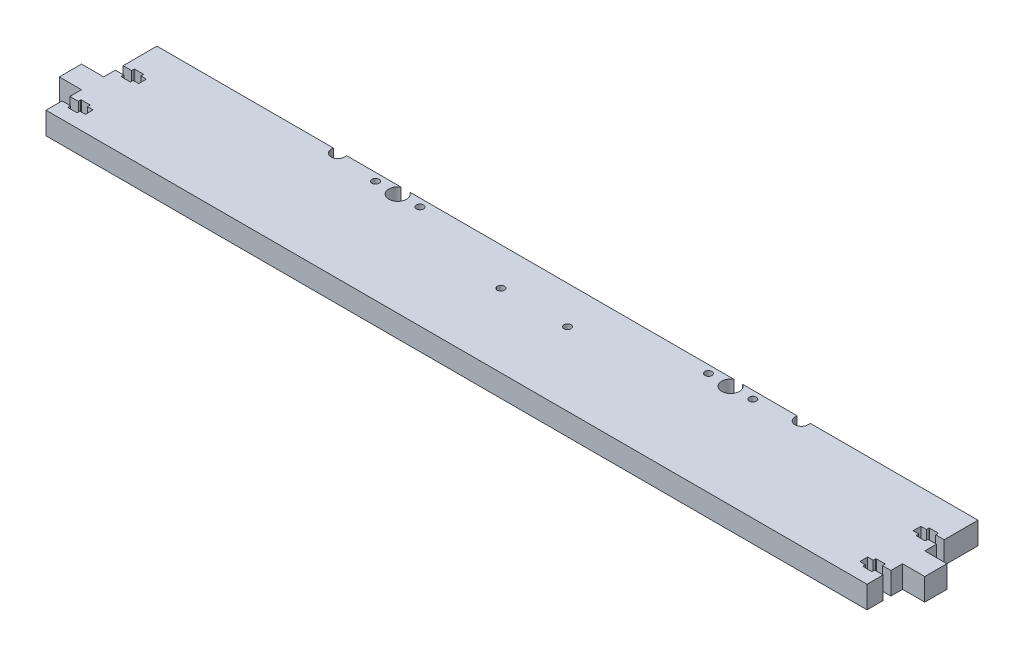
SolidWorks part; units mm, degrees
ref_plane "Front Plane" through (0, 0, 0) normal (0, 0, 1) x (1, 0, 0)
ref_plane "Top Plane" through (0, 0, 0) normal (0, 1, 0) x (1, 0, 0)
ref_plane "Right Plane" through (0, 0, 0) normal (1, 0, 0) x (0, 0, -1)
sketch "Sketch1" plane through (0, 0, 0) normal (0, 1, 0) x (1, 0, 0)
  line L0 (0, 25) -> (0, -25)
  line L1 (-185, 25) -> (0, 25)
  line L2 (-185, 25) -> (-185, -25) construction
  line L3 (-185, -25) -> (0, -25)
  line L4 (-185, -4) -> (-195, -4) construction
  line L5 (-185, 25) -> (0, 0) construction
  line L6 (-185, -25) -> (0, 0) construction
  line L7 (-185, -9) -> (-195, -9)
  line L8 (-195, -9) -> (-195, 1)
  line L9 (-195, 1) -> (-185, 1)
  line L10 (-185, 1) -> (-185, 25)
  line L11 (-185, -9) -> (-185, -25)
  line L47 (0, -25) -> (0, 25) construction
  line L89 (0, -25) -> (0, 25) construction
  point P0 (0, 0)
  dimension "D1" = 185
  dimension "D25" = 25
  dimension "D4" = 50
  dimension "D3" = 21
  dimension "D5" = 10
  dimension "D6" = 10
  dimension "D7" = 5
extrude "MainBody" add sketch "Sketch1" along normal blind 10 contours L3 region at (-93.5428, 0, 0.0428)
sketch "Sketch5" plane through (0, 10, 0) normal (0, 1, 0) x (1, 0, 0)
  line L0 (-185, 8) -> (-174.5, 8) construction
  line L1 (-185, 1) -> (-185, 25) construction
  line L2 (-185, 9.75) -> (-174.5, 9.75) construction
  line L3 (-174.5, 9.75) -> (-174.5, 6.25) construction
  line L4 (-174.5, 6.25) -> (-185, 6.25) construction
  line L5 (-185, 9.75) -> (-181.2, 9.75)
  line L6 (-181.2, 9.75) -> (-181.2, 10.75)
  line L7 (-180.95, 11) -> (-177.25, 11)
  line L8 (-177, 10.75) -> (-177, 9.75)
  line L9 (-177, 9.75) -> (-174.5, 9.75)
  line L10 (-174.5, 9.75) -> (-174.5, 6.25)
  line L11 (-185, 6.25) -> (-185, 9.75)
  line L12 (-195, -9) -> (-195, 1) construction
  line L13 (-185, 6.25) -> (-174.5, 6.25) construction
  line L14 (-177, 6.25) -> (-174.5, 6.25)
  line L15 (-177, 5.25) -> (-177, 6.25)
  line L16 (-180.95, 5) -> (-177.25, 5)
  line L17 (-181.2, 6.25) -> (-181.2, 5.25)
  line L18 (-185, 6.25) -> (-181.2, 6.25)
  line L19 (-185, 1) -> (-185, -9) construction
  line L20 (-195, -4) -> (-185, -4) construction
  line L21 (-195, -9) -> (-195, 1) construction
  line L22 (-185, -14.25) -> (-174.5, -14.25) construction
  line L23 (-174.5, -14.25) -> (-185, -14.25) construction
  line L24 (-174.5, -17.75) -> (-174.5, -14.25) construction
  line L25 (-185, -17.75) -> (-174.5, -17.75) construction
  line L26 (-185, -16) -> (-174.5, -16) construction
  line L27 (-185, -14.25) -> (-181.2, -14.25)
  line L28 (-181.2, -14.25) -> (-181.2, -13.25)
  line L29 (-180.95, -13) -> (-177.25, -13)
  line L30 (-177, -13.25) -> (-177, -14.25)
  line L31 (-177, -14.25) -> (-174.5, -14.25)
  line L32 (-185, -14.25) -> (-185, -17.75)
  line L33 (-174.5, -17.75) -> (-174.5, -14.25)
  line L34 (-177, -17.75) -> (-174.5, -17.75)
  line L35 (-177, -18.75) -> (-177, -17.75)
  line L36 (-180.95, -19) -> (-177.25, -19)
  line L37 (-181.2, -17.75) -> (-181.2, -18.75)
  line L38 (-185, -17.75) -> (-181.2, -17.75)
  line L39 (-185, 6.25) -> (-174.5, 6.25) construction
  arc A0 (-177.25, 11) -> (-177, 10.75) centre (-177.25, 10.75) cw
  arc A1 (-181.2, 10.75) -> (-180.95, 11) centre (-180.95, 10.75) cw
  arc A2 (-181.2, 5.25) -> (-180.95, 5) centre (-180.95, 5.25) ccw
  arc A3 (-177.25, 5) -> (-177, 5.25) centre (-177.25, 5.25) ccw
  arc A4 (-177.25, -13) -> (-177, -13.25) centre (-177.25, -13.25) cw
  arc A5 (-181.2, -13.25) -> (-180.95, -13) centre (-180.95, -13.25) cw
  arc A6 (-181.2, -18.75) -> (-180.95, -19) centre (-180.95, -18.75) ccw
  arc A7 (-177.25, -19) -> (-177, -18.75) centre (-177.25, -18.75) ccw
  point P6 (-195, -4)
  point P17 (-177, 11)
  point P20 (-181.2, 11)
  point P29 (-181.2, 5)
  point P30 (-177, 5)
  point P61 (-177, -13)
  point P62 (-181.2, -13)
  point P63 (-181.2, -19)
  point P64 (-177, -19)
  dimension "D8" = 0.25
  dimension "D1" = 10.5
  dimension "D2" = 1.75
  dimension "D4" = 4.2
  dimension "D5" = 8
  dimension "D6" = 3
  dimension "D7" = 12
extrude "ScrewCutouts" cut sketch "Sketch5" against normal through all
mirror "Mirror1" about plane through (0, 0, 0) normal (1, 0, 0) of "ScrewCutouts", "MainBody"
sketch "Sketch3" plane through (0, 10, 0) normal (0, 1, 0) x (1, 0, 0)
  line L0 (2, 25) -> (2, -25) construction
  line L1 (-185, 25) -> (185, 25) construction
  line L2 (-185, -25) -> (185, -25) construction
  line L3 (-63, 21.5) -> (-83, 21.5) construction
  line L4 (-73, 17.5) -> (-73, 25.5) construction
  line L5 (77, 17.5) -> (77, 25.5) construction
  line L6 (67, 21.5) -> (87, 21.5) construction
  circle A0 centre (-73, 21.5) radius 4
  circle A1 centre (-83, 21.5) radius 1.6
  circle A2 centre (-63, 21.5) radius 1.6
  circle A3 centre (67, 21.5) radius 1.6
  circle A4 centre (87, 21.5) radius 1.6
  circle A5 centre (77, 21.5) radius 4
  dimension "D2" = 8
  dimension "D4" = 3.2
  dimension "D1" = 3.5
  dimension "D3" = 10
  dimension "D5" = 75
  dimension "D6" = 2
extrude "RodCutouts" cut sketch "Sketch3" against normal through all
sketch "Sketch6" plane through (0, 10, 0) normal (0, 1, 0) x (1, 0, 0)
  line L0 (-73, 21.5) -> (77, 21.5) construction
  line L1 (2, 21.5) -> (2, -25) construction
  line L2 (-185, -25) -> (185, -25) construction
  line L3 (17, 8) -> (-13, 8) construction
  line L4 (-71.0635, 25) -> (75.0635, 25) construction
  circle A0 centre (-13, 8) radius 1.6
  circle A1 centre (17, 8) radius 1.6
  point P13 (2, 8)
  dimension "D1" = 3.2
  dimension "D2" = 15
  dimension "D3" = 17
extrude "Cut-Extrude1" cut sketch "Sketch6" against normal through all
sketch "Sketch7" plane through (0, 10, 0) normal (0, 1, 0) x (1, 0, 0)
  line L0 (-73, 21.5) -> (77, 21.5) construction
  line L1 (2, 21.5) -> (2, -25) construction
  line L3 (-102.5, 25) -> (-102.5, 24) construction
  line L4 (-185, 25) -> (-74.9365, 25) construction
  line L5 (-99.5, 25) -> (-99.5, 24)
  line L6 (-105.5, 25) -> (-105.5, 24)
  line L7 (106.5, 25) -> (106.5, 24) construction
  line L8 (103.5, 25) -> (103.5, 24)
  line L9 (109.5, 25) -> (109.5, 24)
  line L12 (-185, -25) -> (185, -25) construction
  arc A0 (-99.5, 25) -> (-105.5, 25) centre (-102.5, 25) ccw
  arc A1 (-105.5, 24) -> (-99.5, 24) centre (-102.5, 24) ccw
  arc A2 (103.5, 25) -> (109.5, 25) centre (106.5, 25) cw
  arc A3 (109.5, 24) -> (103.5, 24) centre (106.5, 24) cw
  point P12 (-102.5, 24.5)
  point P19 (106.5, 24.5)
  dimension "D1" = 3
  dimension "D2" = 1
  dimension "D3" = 104.5
extrude "BedAdjustmentScrewCutout" cut sketch "Sketch7" against normal through all
equation "\"Y-ROD-SPACING\"=75"
equation "\"Y-BED-OFFSET\"=2"
equation "\"T-SLOT-NUT-FILLET-RADIUS\"=0.25"
equation "\"T-SLOT-SCREW-SHAFT-RADIUS\"=1.75"
equation "\"T-SLOT-SCREW-SHAFT-CUTOUT-LENGTH\"=10.5"
equation "\"T-SLOT-NUT-DEPTH\"=4.2"
equation "\"T-SLOT-NUT-WIDTH\"=3"
equation "\"T-SLOT-NUT-END-DISTANCE\"=8"
equation "\"ACRYLIC-TAB-CUTOUT-SIZE\"=\"ACRYLIC-THICKNESS\"+\"ACRYLIC-TAB-TOLERANCE\"*2"
equation "\"ACRYLIC-M3-HOLE\"=3.2"
equation "\"D1@Sketch5\"=\"T-SLOT-SCREW-SHAFT-CUTOUT-LENGTH\""
equation "\"D2@Sketch5\"=\"T-SLOT-SCREW-SHAFT-RADIUS\""
equation "\"D4@Sketch5\"=\"T-SLOT-NUT-DEPTH\""
equation "\"D5@Sketch5\"=\"T-SLOT-NUT-END-DISTANCE\""
equation "\"D6@Sketch5\"=\"T-SLOT-NUT-WIDTH\""
equation "\"D8@Sketch5\"=\"T-SLOT-NUT-FILLET-RADIUS\""
equation "\"D4@Sketch3\"=\"ACRYLIC-M3-HOLE\""
equation "\"D5@Sketch3\"=\"Y-ROD-SPACING\""
equation "\"D6@Sketch3\"=\"Y-BED-OFFSET\""
equation "\"Y-BED-ROD-INSET\"=3.5"
equation "\"D1@Sketch3\"=\"Y-BED-ROD-INSET\""
equation "\"SMOOTHROD-CAP-SCREW-DISTANCE\"=20"
equation "\"D3@Sketch3\"=\"SMOOTHROD-CAP-SCREW-DISTANCE\"/2"
equation "\"ACRYLIC-TAB-WIDTH\"=\"ACRYLIC-THICKNESS\""
equation "\"FRAME-WIDTH-INNER\"=370"
equation "\"D6@Sketch1\"=\"ACRYLIC-TAB-WIDTH\""
equation "\"D5@Sketch1\"=\"ACRYLIC-TAB-WIDTH\""
equation "\"D1@Sketch1\"=\"FRAME-WIDTH-INNER\"/2"
equation "\"X-ROD-SPACING\"=45"
equation "\"Z-ROD-SPACING\"=17.5"
equation "\"ACRYLIC-THICKNESS\"=10"
equation "\"ACRYLIC-THICKNESS2\"=4.5"
equation "\"NEMA17-HOLE-SPACING\"=31"
equation "\"NEMA17-CENTRAL-CUTOUT\"=22.5"
equation "\"Z-BRACKET-REACH\"=55"
equation "\"TOP-BRACKET-SPACING\"=40"
equation "\"SMOOTHROD-X-LENGTH\"=350"
equation "\"SMOOTHROD-Y-LENGTH\"=350"
equation "\"SMOOTHROD-Z-LENGTH\"=350"
equation "\"SMOOTHROD-TIGHTENING-HEADROOM\"=1"
equation "\"LEADSCREW-Z-LENGTH\"=300"
equation "\"SCREW-LENGTH-FRAME\"=\"ACRYLIC-THICKNESS\" + 10"
equation "\"SCREW-HEAD-RADIUS\"=6"
equation "\"PRINTED-X-SMOOTHROD-DIAMETER\"=8.2"
equation "\"PRINTED-X-SMOOTHROD-CUTOUT\"=10"
equation "\"PRINTED-X-BASE-HEIGHT\"=10"
equation "\"PRINTED-LM8UU-CUTOUT-SIZE\"=16"
equation "\"PRINTED-LM8UU-CUTOUT-LENGTH\"=24.5"
equation "\"PRINTED-X-IDLER-HEIGHT\"=16"
equation "\"PSU-MOUNTING-WIDTH\"=95"
equation "\"PSU-MOUNTING-HEIGHT\"=177"
equation "\"D1@MainBody\"=\"ACRYLIC-THICKNESS\""
equation "\"D7@Sketch1\"=\"ACRYLIC-TAB-WIDTH\"/2"
equation "\"D1@Sketch6\"=\"ACRYLIC-M3-HOLE\""
equation "\"Y-BELT-TO-ROD-DISTANCE\"=20"
equation "\"Y-BED-SCREW-SPACING\"=209"
equation "\"Z-ROD-INSET\"=16"
equation "\"SPOOL-HOLDER-ROD-SPACING\"=150"
equation "\"D3@Sketch7\"=\"Y-BED-SCREW-SPACING\"/2"
equation "\"Y-BED-SCREW-CUTOUT-SLOT-HEIGHT\"=1"
equation "\"D2@Sketch7\"=\"Y-BED-SCREW-CUTOUT-SLOT-HEIGHT\""
